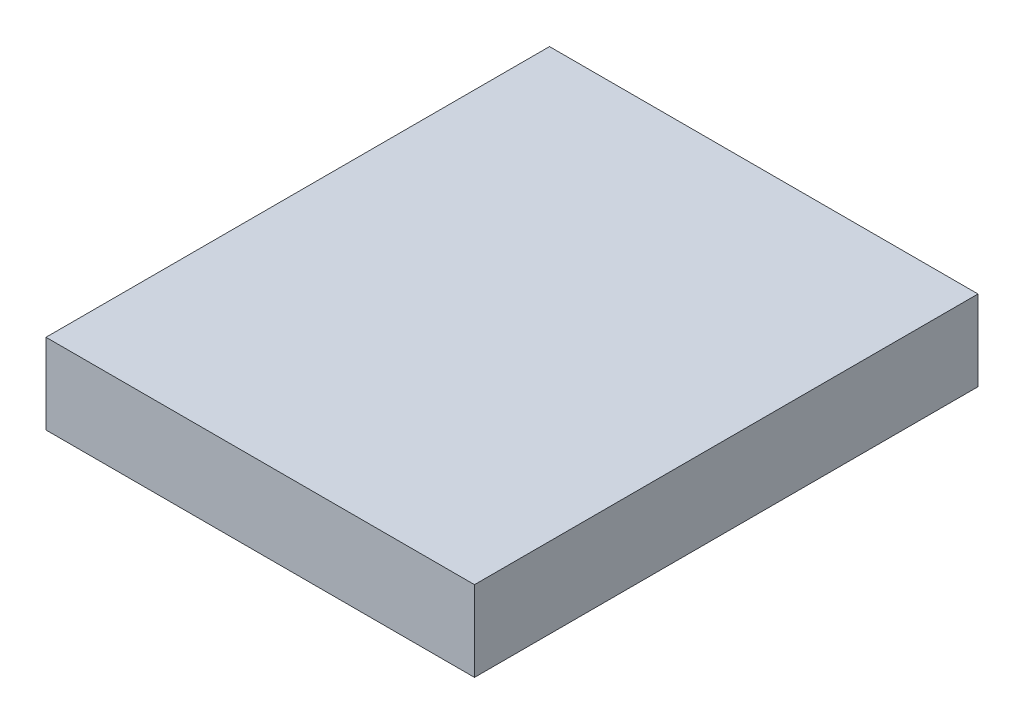
SolidWorks part; units mm, degrees
ref_plane "Front Plane" through (0, 0, 0) normal (0, 0, 1) x (1, 0, 0)
ref_plane "Top Plane" through (0, 0, 0) normal (0, 1, 0) x (1, 0, 0)
ref_plane "Right Plane" through (0, 0, 0) normal (1, 0, 0) x (0, 0, -1)
sketch "Sketch2" plane through (0, 0, 0) normal (0, 1, 0) x (1, 0, 0)
  line L1 (-25.4, 29.845) -> (25.4, 29.845)
  line L2 (-25.4, 29.845) -> (-25.4, -29.845)
  line L3 (-25.4, -29.845) -> (25.4, -29.845)
  line L4 (25.4, 29.845) -> (25.4, -29.845)
  line L5 (-25.4, 29.845) -> (25.4, -29.845) construction
  line L6 (-25.4, -29.845) -> (25.4, 29.845) construction
  point P0 (0, 0)
  dimension "D1" = 50.8
  dimension "D2" = 59.69
extrude "Boss-Extrude1" add sketch "Sketch2" along normal blind 9.525 contours L2 L3 L4 L1
